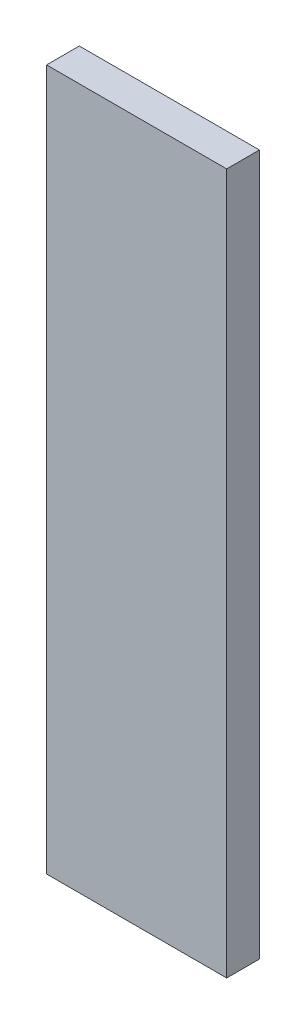
SolidWorks part; units mm, degrees
ref_plane "Front Plane" through (0, 0, 0) normal (0, 0, 1) x (1, 0, 0)
ref_plane "Top Plane" through (0, 0, 0) normal (0, 1, 0) x (1, 0, 0)
ref_plane "Right Plane" through (0, 0, 0) normal (1, 0, 0) x (0, 0, -1)
sketch "Sketch1" plane through (0, 0, 0) normal (0, 1, 0) x (1, 0, 0)
  line L1 (-19.5, 77.5) -> (19.5, 77.5)
  line L2 (-19.5, 77.5) -> (-19.5, -77.5)
  line L3 (-19.5, -77.5) -> (19.5, -77.5)
  line L4 (19.5, 77.5) -> (19.5, -77.5)
  line L5 (-19.5, 77.5) -> (19.5, -77.5) construction
  line L6 (-19.5, -77.5) -> (19.5, 77.5) construction
  point P0 (0, 0)
  dimension "D1" = 39
  dimension "D2" = 155
extrude "Boss-Extrude1" add sketch "Sketch1" along normal blind 2
sketch "Sketch2" plane through (0, 2, 0) normal (0, 1, 0) x (1, 0, 0)
  line L0 (-17.5, -75.5) -> (-17.5, -77.5)
  line L1 (-19.5, 77.5) -> (19.5, 77.5)
  line L2 (-19.5, 77.5) -> (-19.5, -77.5)
  line L3 (-19.5, -77.5) -> (19.5, -77.5)
  line L4 (19.5, 77.5) -> (19.5, -77.5)
  line L5 (-17.5, 75.5) -> (17.5, 75.5)
  line L6 (-17.5, 75.5) -> (-17.5, -75.5)
  line L7 (-17.5, -75.5) -> (17.5, -75.5)
  line L8 (17.5, 75.5) -> (17.5, -75.5)
  line L9 (-17.5, 75.5) -> (17.5, -75.5) construction
  line L10 (-17.5, -75.5) -> (17.5, 75.5) construction
  line L11 (17.5, -75.5) -> (17.5, -77.5)
  point P6 (0, 0)
  line M9 (19.5, -77.5) -> (19.5, 77.5)
  line M10 (19.5, 77.5) -> (-19.5, 77.5)
  line M11 (-19.5, 77.5) -> (-19.5, -77.5)
  line M12 (-19.5, -77.5) -> (19.5, -77.5)
  dimension "D1" = 2
  dimension "D2" = 2
extrude "Boss-Extrude2" add sketch "Sketch2" along normal blind 58 contours L8 L11 L3 L0 L6 L5 M9 M10 M11 M12 region at (-19.0983, 2, 76.5)
sketch "Sketch3" plane through (0, 2, 0) normal (0, 1, 0) x (1, 0, 0)
  line L0 (-17.5, 75.5) -> (-17.5, -77.5) construction
  line L1 (-17.5, -77.5) -> (-15.5, -77.5)
  line L2 (-17.5, -77.5) -> (-17.5, -75.5)
  line L3 (-17.5, -75.5) -> (-15.5, -75.5)
  line L4 (-15.5, -77.5) -> (-15.5, -75.5)
  line L5 (-17.5, -73.3) -> (-15.5, -73.3)
  line L6 (-17.5, -73.3) -> (-17.5, -71.3)
  line L7 (-17.5, -71.3) -> (-15.5, -71.3)
  line L8 (-15.5, -73.3) -> (-15.5, -71.3)
  line L9 (17.5, 75.5) -> (17.5, -77.5) construction
  line L10 (17.5, -77.5) -> (15.5, -77.5)
  line L11 (17.5, -77.5) -> (17.5, -75.5)
  line L12 (17.5, -75.5) -> (15.5, -75.5)
  line L13 (15.5, -77.5) -> (15.5, -75.5)
  line L14 (17.5, -73.3) -> (15.5, -73.3)
  line L15 (17.5, -73.3) -> (17.5, -71.3)
  line L16 (17.5, -71.3) -> (15.5, -71.3)
  line L17 (15.5, -73.3) -> (15.5, -71.3)
  line L18 (15.5, -75.5) -> (15.5, -73.3) construction
  line L19 (-15.5, -73.3) -> (15.5, -73.3) construction
  line L20 (-15.5, -75.5) -> (-15.5, -73.3) construction
  line L21 (-15.5, -75.5) -> (15.5, -75.5) construction
  line L22 (15.5, -71.3) -> (-15.5, -71.3) construction
  dimension "D1" = 2
  dimension "D2" = 2
  dimension "D3" = 2.2
  dimension "D4" = 2
extrude "Boss-Extrude3" add sketch "Sketch3" along normal up to surface (58 mm away) up to face at (0, 60, 0.5)
sketch "Sketch4" plane through (0, 0, -75.5) normal (0, 0, 1) x (1, 0, 0)
  line L0 (-17.5, 60) -> (-15.5, 60)
  line L1 (-17.5, 60) -> (17.5, 60) construction
  line L2 (-15.5, 60) -> (-15.5, 58)
  line L3 (-15.5, 58) -> (-17.5, 58)
  line L5 (-17.5, 58) -> (-17.5, 60)
  line L7 (-17.5, 60) -> (-17.5, 2) construction
  line L8 (-15.5, 53.8) -> (-17.5, 51.8)
  line L9 (-17.5, 51.8) -> (-17.5, 55.8)
  line L10 (-15.5, 53.8) -> (-15.5, 55.8)
  line L11 (-15.5, 55.8) -> (-17.5, 55.8)
  line L12 (0, 0) -> (0, 60) construction
  line L13 (15.5, 55.8) -> (17.5, 55.8)
  line L14 (15.5, 53.8) -> (15.5, 55.8)
  line L15 (17.5, 51.8) -> (17.5, 55.8)
  line L16 (15.5, 53.8) -> (17.5, 51.8)
  line L17 (17.5, 58) -> (17.5, 60)
  line L18 (15.5, 58) -> (17.5, 58)
  line L19 (15.5, 60) -> (15.5, 58)
  line L20 (17.5, 60) -> (15.5, 60)
  dimension "D1" = 2
  dimension "D2" = 2
  dimension "D3" = 45
  dimension "D4" = 2.2
  dimension "D5" = 2
extrude "Boss-Extrude4" add sketch "Sketch4" along normal up to surface (153 mm away)
sketch "Sketch5" plane through (0, 2, 0) normal (0, 1, 0) x (1, 0, 0)
  line L1 (-15.5, -77.5) -> (15.5, -77.5)
  line L2 (-15.5, -77.5) -> (-15.5, -75.5)
  line L3 (-15.5, -75.5) -> (15.5, -75.5)
  line L4 (15.5, -77.5) -> (15.5, -75.5)
  line L5 (-15.5, -71.3) -> (15.5, -71.3)
  line L6 (-15.5, -71.3) -> (-15.5, -73.3)
  line L7 (-15.5, -73.3) -> (15.5, -73.3)
  line L8 (15.5, -71.3) -> (15.5, -73.3)
sketch "Sketch6" plane through (0, 0, -75.5) normal (0, 0, 1) x (1, 0, 0)
  line L0 (-17.5, 58) -> (-15.5, 58) construction
  line L1 (-17.5, 58) -> (17.5, 58)
  line L2 (-17.5, 58) -> (-17.5, 55.8)
  line L3 (-17.5, 55.8) -> (17.5, 55.8)
  line L4 (17.5, 58) -> (17.5, 55.8)
  line L5 (-17.5, 58) -> (-17.5, 55.8) construction
  line L6 (-15.5, 55.8) -> (-17.5, 55.8) construction
extrude "Cut-Extrude1" cut sketch "Sketch6" along normal through all
sketch "Sketch7" plane through (0, 2, 0) normal (0, 1, 0) x (1, 0, 0)
  line L1 (-17.5, -75.5) -> (17.5, -75.5)
  line L2 (-17.5, -75.5) -> (-17.5, -73.3)
  line L3 (-17.5, -73.3) -> (17.5, -73.3)
  line L4 (17.5, -75.5) -> (17.5, -73.3)
extrude "Cut-Extrude2" cut sketch "Sketch7" along normal through all
extrude "Boss-Extrude5" add sketch "Sketch5" along normal blind 2
sketch "Sketch8" plane through (0, 0, 0) normal (1, 0, 0) x (0, 0, -1)
  line L0 (75.5, 60) -> (73.5, 60)
  line L1 (-73.3, 60) -> (75.5, 60) construction
  line L2 (73.5, 60) -> (73.5, 58)
  line L3 (-73.3, 58) -> (75.5, 58) construction
  line L4 (73.5, 58) -> (75.5, 58)
  line L5 (75.5, 58) -> (75.5, 60)
  line L6 (75.5, 55.8) -> (73.5, 55.8)
  line L7 (-73.3, 55.8) -> (75.5, 55.8) construction
  line L8 (73.5, 55.8) -> (73.5, 53.8)
  line L9 (-71.3, 53.8) -> (75.5, 53.8) construction
  line L10 (73.5, 53.8) -> (75.5, 51.8)
  line L11 (75.5, 51.8) -> (75.5, 55.8)
  dimension "D1" = 2
extrude "Boss-Extrude6" add sketch "Sketch8" along normal up to surface and the other way up to surface up to face at (17.5, 26.9, -2.1) other way up to face at (-17.5, 26.9, -2.1)
sketch "Sketch10" plane through (-17.5, 0, 0) normal (1, 0, 0) x (0, 0, -1)
  line L1 (-75.5, 55.8) -> (-77.5, 55.8)
  line L2 (-75.5, 55.8) -> (-75.5, 58)
  line L3 (-75.5, 58) -> (-77.5, 58)
  line L4 (-77.5, 55.8) -> (-77.5, 58)
  line L5 (-73.3, 60) -> (-75.5, 60)
  line L6 (-73.3, 60) -> (-73.3, 58)
  line L7 (-73.3, 58) -> (-75.5, 58)
  line L8 (-75.5, 60) -> (-75.5, 58)
  line M1 (-75.5, 60) -> (-75.5, 58)
  line M2 (-75.5, 58) -> (-77.5, 58)
  line M3 (-77.5, 58) -> (-77.5, 55.8)
  line M4 (-77.5, 55.8) -> (-75.5, 55.8)
  line M11 (-73.3, 58) -> (-73.3, 60)
  line M12 (-73.3, 60) -> (-75.5, 60)
extrude "Boss-Extrude8" add sketch "Sketch10" along normal up to surface (2 mm away) contours L2 M4 M2 M3 | L7 M11 M12 M1 region at (-17.5, 59, 74.4) region at (-17.5, 56.9, 76.5) up to face at (-15.5, 59, -0.1)
sketch "Sketch11" plane through (17.5, 0, 0) normal (-1, 0, 0) x (0, 0, 1)
  line L1 (75.5, 55.8) -> (77.5, 55.8)
  line L2 (75.5, 55.8) -> (75.5, 58)
  line L3 (75.5, 58) -> (77.5, 58)
  line L4 (77.5, 55.8) -> (77.5, 58)
  line L5 (73.3, 60) -> (75.5, 60)
  line L6 (73.3, 60) -> (73.3, 58)
  line L7 (73.3, 58) -> (75.5, 58)
  line L8 (75.5, 60) -> (75.5, 58)
  line M2 (75.5, 55.8) -> (77.5, 55.8)
  line M3 (77.5, 55.8) -> (77.5, 58)
  line M4 (77.5, 58) -> (75.5, 58)
  line M5 (75.5, 58) -> (75.5, 60)
  line M6 (75.5, 60) -> (73.3, 60)
  line M7 (73.3, 60) -> (73.3, 58)
extrude "Boss-Extrude9" add sketch "Sketch11" along normal up to surface (2 mm away) contours L2 M2 M3 M4 | L7 M7 M5 M6 region at (17.5, 56.9, 76.5) region at (17.5, 59, 74.4) up to face at (15.5, 59, -0.1)
fillet "Fillet2" radius 2.5 17 edges at (-17.5, 26.9, 71.3) (17.5, 26.9, 71.3) (19.5, 30, 77.5) (-19.5, 30, 77.5) (-19.5, 30, -77.5) (-17.5, 26.9, -75.5) (17.5, 26.9, -75.5) (19.5, 30, -77.5) (-19.5, 60, 0) (0, 60, -77.5) (19.5, 60, 0) (0, 0, -77.5) (0, 0, 77.5) (-19.5, 0, 0) (19.5, 0, 0) (-17.5, 60, 77.5) (17.5, 60, 77.5)
sketch "Sketch13" plane through (0, 0, -77.5) normal (0, 0, -1) x (-1, 0, 0)
  line L0 (15.5, 57.5) -> (15.5, 4) construction
  line L1 (-15.5, 7) -> (15.5, 7)
  line L2 (-15.5, 7) -> (-15.5, 4)
  line L3 (-15.5, 4) -> (15.5, 4)
  line L4 (15.5, 7) -> (15.5, 4)
  dimension "D1" = 3
sketch "Sketch14" plane through (0, 0, -75.5) normal (0, 0, 1) x (1, 0, 0)
  line L1 (-18.25, 9) -> (18.25, 9)
  line L2 (-18.25, 9) -> (-18.25, 1.25)
  line L3 (-18.25, 1.25) -> (18.25, 1.25)
  line L4 (18.25, 9) -> (18.25, 1.25)
  line L5 (15.5, 7) -> (-15.5, 7) construction
  line L7 (17, 0) -> (17, 2.5) construction
  line L8 (19.5, 2.5) -> (17, 2.5) construction
  line L10 (-19.5, 2.5) -> (-17, 2.5) construction
  point P20 (17, 1.25)
  point P23 (18.25, 2.5)
  point P26 (-18.25, 2.5)
  dimension "D1" = 2
extrude "Boss-Extrude10" add sketch "Sketch14" along normal blind 2
extrude "Cut-Extrude4" cut sketch "Sketch13" against normal blind 2
fillet "Fillet3" radius 2 1 edges at (0, 9, -73.5)
fillet "Fillet4" radius 0.5 12 edges at (0, 4, -77.5) (0, 7, -77.5) (15.5, 7, -76.5) (15.5, 4, -76.5) (15.5, 5.5, -77.5) (-15.5, 4, -76.5) (-15.5, 7, -76.5) (-15.5, 5.5, -77.5) (0, 7, -75.5) (-15.5, 5.5, -75.5) (0, 4, -75.5) (15.5, 5.5, -75.5)
sketch "Sketch15" plane through (0, 0, 0) normal (0, -1, 0) x (1, 0, 0)
  line L0 (0, 77.5) -> (0, 0) construction
  line L1 (-17, 77.5) -> (17, 77.5) construction
  line L2 (0, 0) -> (0, -77.5) construction
  line L4 (17, -77.5) -> (-17, -77.5) construction
  circle A0 centre (0, 38.75) radius 5.1
  circle A1 centre (0, -38.75) radius 5.1
  dimension "D1" = 10.2
extrude "Cut-Extrude5" cut sketch "Sketch15" against normal through all
sketch "Sketch16" plane through (0, 2, 0) normal (0, 1, 0) x (1, 0, 0)
  circle A0 centre (0, 38.75) radius 7.1
  circle A1 centre (0, -38.75) radius 7.1
  circle A2 centre (0, 38.75) radius 5.1 construction
  dimension "D1" = 2
extrude "Boss-Extrude11" add sketch "Sketch16" along normal blind 1
fillet "Fillet5" radius 0.5 4 edges at (0, 2, 45.85) (0, 2, -31.65) (0, 3, 45.85) (0, 3, -31.65)
fillet "Fillet7" radius 0.5 8 edges at (15.5, 30.75, 77.5) (15.5, 60, 0.75) (-15.5, 60, 0.75) (-15.5, 30.75, 77.5) (0, 4, 77.5) (0, 60, -73.5) (15.5, 59.2678, 76.7678) (-15.5, 59.2678, 76.7678)
sketch "Sketch17" plane through (0, 0, 0) normal (0, 0, 1) x (1, 0, 0)
  line L0 (15, 9) -> (-15, 9) construction
  line L1 (-19.5, 60) -> (19.5, 60)
  line L2 (-19.5, 60) -> (-19.5, 0)
  line L3 (-19.5, 0) -> (19.5, 0)
  line L4 (19.5, 60) -> (19.5, 0)
  line L5 (-14.5, 9) -> (14.5, 9)
  line L6 (-14.5, 9) -> (-14.5, 60)
  line L7 (-14.5, 60) -> (14.5, 60)
  line L8 (14.5, 9) -> (14.5, 60)
  line L9 (-16, 60) -> (16, 60) construction
  line L10 (0, 0) -> (0, 9) construction
  line L11 (-19.5, 2.5) -> (-19.5, 57.5) construction
  dimension "D1" = 29
extrude "Cut-Extrude6" cut sketch "Sketch17" against normal through all both and the other way through all contours L10 L3 L4 L1 L8 L5 | L3 L10 L5 L6 L1 L2 region at (-17, 59.3691, 0) region at (17, 59.3691, 0)
sketch "Sketch18" plane through (0, 0, 0) normal (0, 0, 1) x (1, 0, 0)
  line L1 (14.5, 9) -> (-14.5, 9)
  line L2 (14.5, 9) -> (14.5, 60)
  line L3 (14.5, 60) -> (-14.5, 60)
  line L4 (-14.5, 9) -> (-14.5, 60)
  line L5 (14.5, 9) -> (-14.5, 60) construction
  line L6 (14.5, 60) -> (-14.5, 9) construction
  line L7 (5.5, 9) -> (-5.5, 9)
  line L8 (5.5, 9) -> (5.5, 60)
  line L9 (5.5, 60) -> (-5.5, 60)
  line L10 (-5.5, 9) -> (-5.5, 60)
  line L11 (5.5, 9) -> (-5.5, 60) construction
  line L12 (5.5, 60) -> (-5.5, 9) construction
  point P0 (0, 34.5)
  point P5 (0, 34.5)
  dimension "D1" = 11
extrude "Cut-Extrude7" cut sketch "Sketch18" against normal through all contours L1 L10 L3 L4 | L8 L1 L2 L3 region at (10, 34.5, 0) region at (-10, 34.5, 0)
sketch "Sketch19" plane through (0, 0, -75.5) normal (0, 0, 1) x (1, 0, 0)
  line L1 (-5.5, 60) -> (5.5, 60)
  line L2 (-5.5, 60) -> (-5.5, 51.8)
  line L3 (-5.5, 51.8) -> (5.5, 51.8)
  line L4 (5.5, 60) -> (5.5, 51.8)
extrude "Cut-Extrude8" cut sketch "Sketch19" against normal through all both and the other way through all
